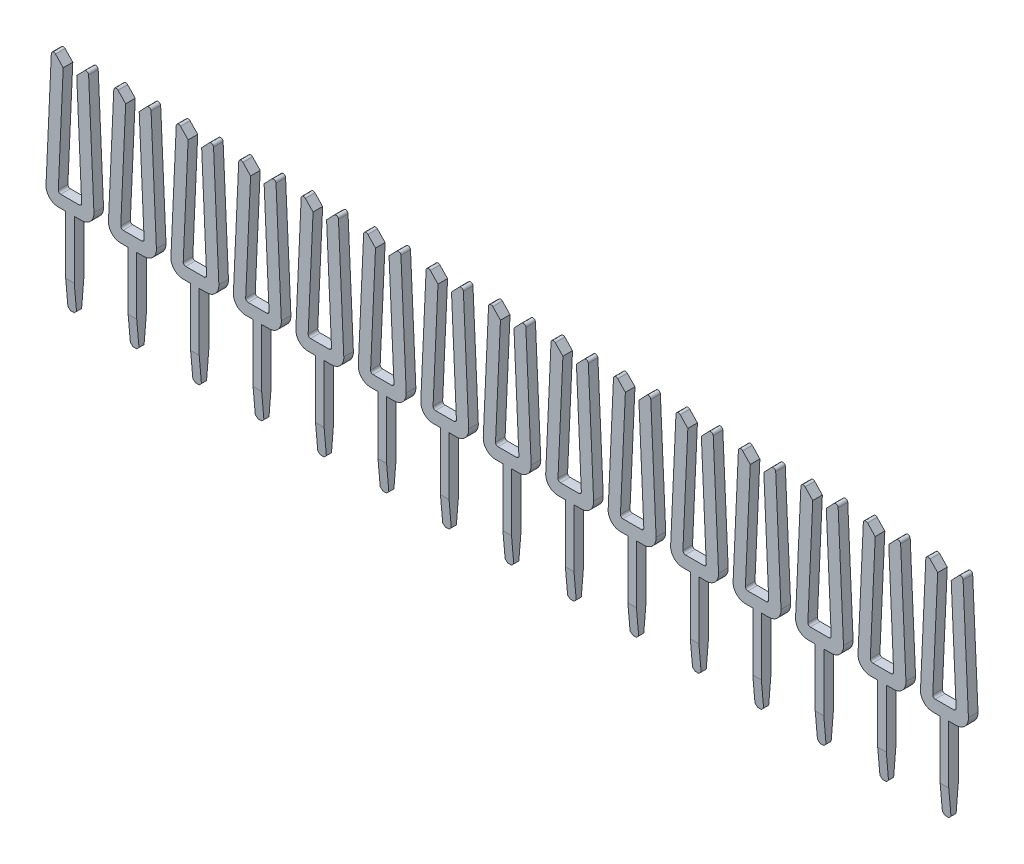
SolidWorks part; units mm, degrees
other "Шпилька"
ref_plane "Front Plane" through (0, 0, 0) normal (0, 0, 1) x (1, 0, 0)
ref_plane "Top Plane" through (0, 0, 0) normal (0, 1, 0) x (1, 0, 0)
ref_plane "Right Plane" through (0, 0, 0) normal (1, 0, 0) x (0, 0, -1)
sketch "Эскиз-Шпилька" plane through (0, 0, 0) normal (0, 0, 1) x (1, 0, 0)
  line L0 (-0.2751, 4.5045) -> (-0.586, 4.8299)
  line L1 (-0.7582, 4.7653) -> (-0.9745, 0.0228)
  line L2 (-0.475, -0.5) -> (-0.175, -0.5)
  line L3 (-0.175, -0.5) -> (-0.175, -3.9)
  line L4 (-0.175, -3.9) -> (-0.075, -4)
  line L5 (0, 4.5045) -> (0, -4) construction
  line L6 (-0.375, 0) -> (0.375, 0)
  line L7 (-0.4749, 0.1045) -> (-0.2751, 4.5045)
  line L8 (0.4749, 0.1045) -> (0.2751, 4.5045)
  line L9 (0.175, -3.9) -> (0.075, -4)
  line L10 (0.175, -0.5) -> (0.175, -3.9)
  line L11 (0.475, -0.5) -> (0.175, -0.5)
  line L12 (0.7582, 4.7653) -> (0.9745, 0.0228)
  line L13 (0.2751, 4.5045) -> (0.586, 4.8299)
  line L14 (-0.075, -4) -> (0.075, -4)
  arc A0 (-0.9745, 0.0228) -> (-0.475, -0.5) centre (-0.475, 0) ccw
  arc A1 (-0.4749, 0.1045) -> (-0.375, 0) centre (-0.375, 0.1) ccw
  arc A2 (-0.586, 4.8299) -> (-0.7582, 4.7653) centre (-0.6583, 4.7608) ccw
  arc A3 (0.586, 4.8299) -> (0.7582, 4.7653) centre (0.6583, 4.7608) cw
  arc A4 (0.4749, 0.1045) -> (0.375, 0) centre (0.375, 0.1) cw
  arc A5 (0.9745, 0.0228) -> (0.475, -0.5) centre (0.475, 0) cw
  point P26 (0, 0)
  point P29 (0, 0)
  point P30 (0, 0)
  point P31 (0, 0)
  point P32 (0, 0)
  point P33 (0, 0)
  point P34 (0, 0)
  point P35 (0, 0)
  point P37 (0, -4)
  dimension "D1" = 2.6
  dimension "D2" = 0.1
  dimension "D6" = 0.1
  dimension "D8" = 0.5
  dimension "D3" = 0.45
  dimension "D4" = 133.7
  dimension "D5" = 4.4
  dimension "D7" = 0.375
  dimension "D9" = 0.3
  dimension "D10" = 3.5
  dimension "D11" = 0.1
  dimension "D12" = 0.1
  dimension "D13" = 0.35
  dimension "D14" = 0.5
extrude "Бобышка-Шпилька" add sketch "Эскиз-Шпилька" along normal blind 0.195 and the other way blind 0.195
chamfer "Фаска1" distance 0.1 angle 85 1 edges at (0, -4, 0.195) first distance on face at (0, -4, 0)
chamfer "Фаска2" distance 0.1 angle 85 1 edges at (0, -4, -0.195) first distance on face at (0, -4, -0.05)
pattern_linear "Линейный массив1" count 15 spacing 2.54 along (-1, 0, 0) of "Бобышка-Шпилька"
